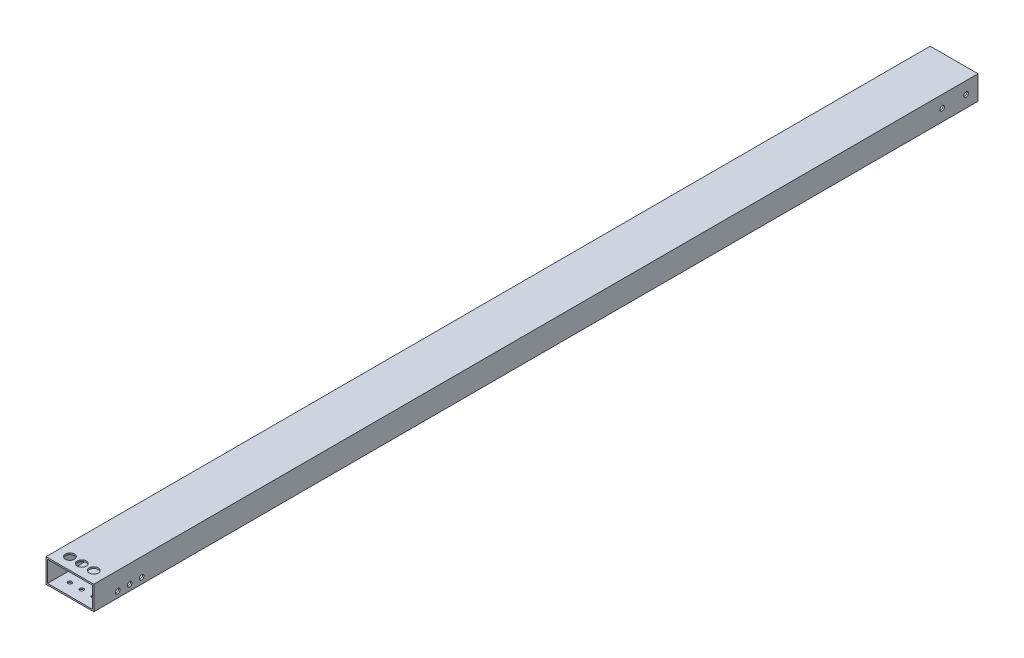
SolidWorks part; units mm, degrees
material "6061-T6 (SS)"
ref_plane "Front Plane" through (0, 0, 0) normal (0, 0, 1) x (1, 0, 0)
ref_plane "Top Plane" through (0, 0, 0) normal (0, 1, 0) x (1, 0, 0)
ref_plane "Right Plane" through (0, 0, 0) normal (1, 0, 0) x (0, 0, -1)
sketch "Sketch1" plane through (0, 0, 0) normal (0, 0, 1) x (1, 0, 0)
  line L0 (-23.8125, 11.1125) -> (23.8125, 11.1125)
  line L1 (-25.4, -12.7) -> (25.4, -12.7)
  line L2 (-25.4, -12.7) -> (-25.4, 12.7)
  line L3 (-25.4, 12.7) -> (25.4, 12.7)
  line L4 (25.4, -12.7) -> (25.4, 12.7)
  line L5 (-25.4, -12.7) -> (25.4, 12.7) construction
  line L6 (-25.4, 12.7) -> (25.4, -12.7) construction
  line L7 (23.8125, -11.1125) -> (23.8125, 11.1125)
  line L8 (-23.8125, -11.1125) -> (23.8125, -11.1125)
  line L9 (-23.8125, -11.1125) -> (-23.8125, 11.1125)
  point P0 (0, 0)
  dimension "D1" = 50.8
  dimension "D2" = 25.4
  dimension "D3" = 1.5875
extrude "Boss-Extrude1" add sketch "Sketch1" along normal mid plane 939.8
sketch "Sketch4" plane through (0, 12.7, 0) normal (0, 1, 0) x (1, 0, 0)
  line L0 (25.4, -469.9) -> (-25.4, -469.9) construction
  circle A0 centre (-12.7, -457.2) radius 4.826
  circle A1 centre (0, -457.2) radius 4.826
  circle A2 centre (12.7, -457.2) radius 4.826
  dimension "D1" = 9.652
  dimension "D2" = 12.7
  dimension "D3" = 12.7
  dimension "D4" = 12.7
extrude "Cut-Extrude3" cut sketch "Sketch4" against normal up to surface (1.5875 mm away) contours A0 | A1 | A2 region at (-12.7, 12.7, 457.2) region at (0, 12.7, 457.2) region at (12.7, 12.7, 457.2) up to face at (0, 11.1125, 0)
sketch "Sketch5" plane through (0, -12.7, 0) normal (0, -1, 0) x (1, 0, 0)
  circle A0 centre (-12.7, 457.2) radius 4.826 construction
  circle A1 centre (0, 457.2) radius 4.826 construction
  circle A2 centre (12.7, 457.2) radius 4.826 construction
  circle A3 centre (-12.7, 457.2) radius 4.826
  circle A4 centre (0, 457.2) radius 4.826
  circle A5 centre (12.7, 457.2) radius 4.826
  circle A6 centre (-12.7, 457.2) radius 2.0193
  circle A7 centre (0, 457.2) radius 2.0193
  circle A8 centre (12.7, 457.2) radius 2.0193
  dimension "D1" = 4.0386
  dimension "D2" = 4.0386
  dimension "D3" = 4.0386
extrude "Cut-Extrude4" cut sketch "Sketch5" against normal up to surface (1.5875 mm away) contours A8 | A7 | A6 region at (-12.7, -12.7, 457.2) region at (0, -12.7, 457.2) region at (12.7, -12.7, 457.2) up to face at (0, -11.1125, 0)
sketch "Sketch6" plane through (0, -12.7, 0) normal (0, -1, 0) x (1, 0, 0)
  line L0 (-25.4, -469.9) -> (25.4, -469.9) construction
  circle A0 centre (-12.7, -457.2) radius 2.0193
  circle A1 centre (0, -457.2) radius 2.0193
  circle A2 centre (12.7, -457.2) radius 2.0193
  dimension "D1" = 4.0386
  dimension "D2" = 12.7
  dimension "D3" = 12.7
  dimension "D4" = 12.7
extrude "Cut-Extrude5" cut sketch "Sketch6" against normal up to surface (1.5875 mm away) contours A2 | A1 | A0 region at (-12.7, -12.7, -457.2) region at (0, -12.7, -457.2) region at (12.7, -12.7, -457.2) up to face at (12.7, -11.1125, 459.2193)
sketch "Sketch7" plane through (25.4, 0, 0) normal (1, 0, 0) x (0, 0, -1)
  line L0 (-469.9, -12.7) -> (-469.9, 12.7) construction
  line L1 (-469.9, 12.7) -> (469.9, 12.7) construction
  line L2 (469.9, -12.7) -> (469.9, 12.7) construction
  line L3 (-469.9, -12.7) -> (469.9, -12.7) construction
  circle A0 centre (-457.2, -6.35) radius 2.4892
  circle A1 centre (-444.5, -6.35) radius 2.4892
  circle A2 centre (-431.8, -6.35) radius 2.4892
  circle A3 centre (-419.1, -6.35) radius 2.4892
  circle A4 centre (457.2, 0) radius 2.4892
  circle A5 centre (444.5, 0) radius 2.4892
  circle A6 centre (431.8, 0) radius 2.4892
  point P18 (0, 0)
  dimension "D1" = 4.9784
  dimension "D7" = 4.9784
  dimension "D8" = 12.7
  dimension "D2" = 12.7
  dimension "D3" = 12.7
  dimension "D4" = 12.7
  dimension "D5" = 12.7
  dimension "D6" = 19.05
  dimension "D9" = 12.7
  dimension "D10" = 12.7
  dimension "D11" = 12.7
extrude "Cut-Extrude6" cut sketch "Sketch7" against normal through all contours A1 | A2 | A3 | A4 | A6 region at (25.4, -6.35, 444.5) region at (25.4, -6.35, 431.8) region at (25.4, -6.35, 419.1) region at (25.4, 0, -457.2) region at (25.4, 0, -431.8)
